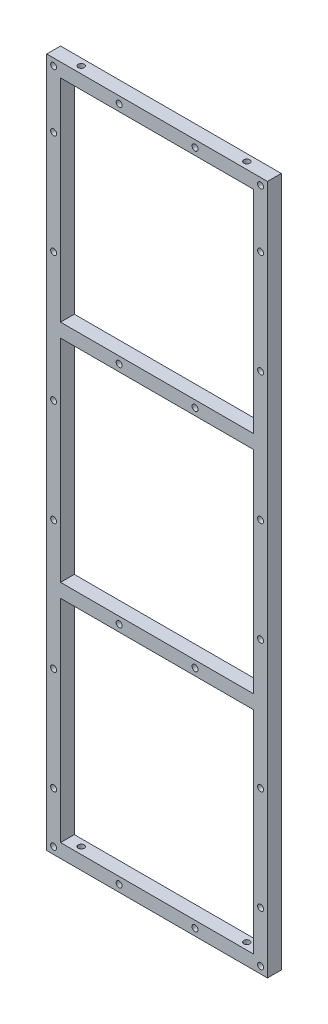
SolidWorks part; units mm, degrees
material "Alumina"
ref_plane "Front Plane" through (0, 0, 0) normal (0, 0, 1) x (1, 0, 0)
ref_plane "Top Plane" through (0, 0, 0) normal (0, 1, 0) x (1, 0, 0)
ref_plane "Right Plane" through (0, 0, 0) normal (1, 0, 0) x (0, 0, -1)
sketch "Sketch1" plane through (0, 0, 0) normal (0, 0, 1) x (1, 0, 0)
  line L0 (42, 144) -> (42, 52)
  line L9 (-48, -150) -> (48, -150)
  line L10 (-48, -150) -> (-48, 150)
  line L11 (-48, 150) -> (48, 150)
  line L12 (48, -150) -> (48, 150)
  line L14 (0, 0) -> (0, 46) construction
  line L15 (-42, -144) -> (42, -144)
  line L17 (-42, 144) -> (42, 144)
  line L19 (-42, 46) -> (-42, -46)
  line L20 (-42, -52) -> (-42, -144)
  line L21 (-42, 52) -> (42, 52)
  line L23 (-42, 46) -> (42, 46)
  line L25 (-42, -46) -> (42, -46)
  line L27 (-42, -52) -> (42, -52)
  line L33 (42, 46) -> (42, -46)
  line L34 (-42, 52) -> (-42, 144)
  line L36 (42, -52) -> (42, -144)
  dimension "D1" = 96
  dimension "D2" = 6
  dimension "D3" = 84
  dimension "D4" = 92
  dimension "D5" = 6
  dimension "D6" = 92
  dimension "D7" = 6
  dimension "D8" = 92
  dimension "D9" = 46
  dimension "D10" = 6
  dimension "D12" = 6
extrude "Boss-Extrude1" add sketch "Sketch1" along normal blind 6
sketch "Sketch2" plane through (0, 0, 6) normal (0, 0, 1) x (1, 0, 0)
  line L0 (-48, 150) -> (-42, 144) construction
  line L1 (42, 144) -> (48, 150) construction
  line L2 (42, -144) -> (48, -150) construction
  line L3 (-42, -144) -> (-48, -150) construction
  line L4 (-45, 147) -> (-45, 49) construction
  circle A0 centre (-45, 147) radius 1.3
  circle A1 centre (45, 147) radius 1.3
  circle A2 centre (-45, 49) radius 1.3
  circle A3 centre (45, 49) radius 1.3
  circle A4 centre (-45, -49) radius 1.3
  circle A5 centre (45, -49) radius 1.3
  circle A6 centre (-45, -147) radius 1.3
  circle A7 centre (45, -147) radius 1.3
  dimension "D1" = 2.6
  dimension "D5" = 2.6
  dimension "D3" = 98
  dimension "D2" = 4
extrude "Cut-Extrude1" cut sketch "Sketch2" against normal blind 6 contours A0 | A1 | A6 | A7
sketch "Sketch3" plane through (0, 0, 6) normal (0, 0, 1) x (1, 0, 0)
  line L0 (48, 150) -> (-48, 150) construction
  line L1 (-48, 150) -> (-48, -150) construction
  line L2 (-45, 122) -> (45, 122) construction
  line L3 (-16.5, 147) -> (-16.5, 49) construction
  line L4 (-45, 122) -> (-45, 77) construction
  line L5 (-45, 122) -> (-45, 21) construction
  circle A0 centre (-45, 122) radius 1.3
  circle A12 centre (-16.5, 147) radius 1.3
  circle A19 centre (16.5, 147) radius 1.3
  circle A20 centre (-16.5, 49) radius 1.3
  circle A21 centre (16.5, 49) radius 1.3
  circle A22 centre (-16.5, -49) radius 1.3
  circle A23 centre (16.5, -49) radius 1.3
  circle A24 centre (-16.5, -147) radius 1.3
  circle A25 centre (16.5, -147) radius 1.3
  circle A26 centre (-45, 21) radius 1.3
  circle A27 centre (45, 122) radius 1.3
  circle A28 centre (45, 77) radius 1.3
  circle A29 centre (-45, 77) radius 1.3
  circle A30 centre (45, 21) radius 1.3
  circle A31 centre (45, -24) radius 1.3
  circle A32 centre (-45, -24) radius 1.3
  circle A33 centre (-45, -80) radius 1.3
  circle A34 centre (45, -80) radius 1.3
  circle A35 centre (45, -125) radius 1.3
  circle A36 centre (-45, -125) radius 1.3
  dimension "D1" = 28
  dimension "D6" = 2.6
  dimension "D3" = 2.6
  dimension "D8" = 3
  dimension "D9" = 33
  dimension "D10" = 31.5
  dimension "D12" = 2.6
  dimension "D13" = 45
  dimension "D14" = 3
  dimension "D2" = 90
  dimension "D7" = 3
  dimension "D11" = 98
  dimension "D16" = 101
  dimension "D4" = 2
  dimension "D5" = 2
  dimension "D15" = 3
sketch "Sketch4" plane through (0, 150, 0) normal (0, 1, 0) x (1, 0, 0)
  line L0 (48, 0) -> (-48, 0) construction
  line L1 (-48, -6) -> (-48, 0) construction
  line L2 (0, -3.3) -> (0, 3.3) construction
  circle A0 centre (-36, -3) radius 1.3
  circle A1 centre (36, -3) radius 1.3
  dimension "D1" = 3
  dimension "D3" = 2.6
  dimension "D2" = 12
extrude "Cut-Extrude5" cut sketch "Sketch4" against normal blind 10
mirror "Mirror1" about plane through (0, 0, 0) normal (0, 1, 0) of "Cut-Extrude5"
extrude "Cut-Extrude6" cut sketch "Sketch3" against normal blind 10
